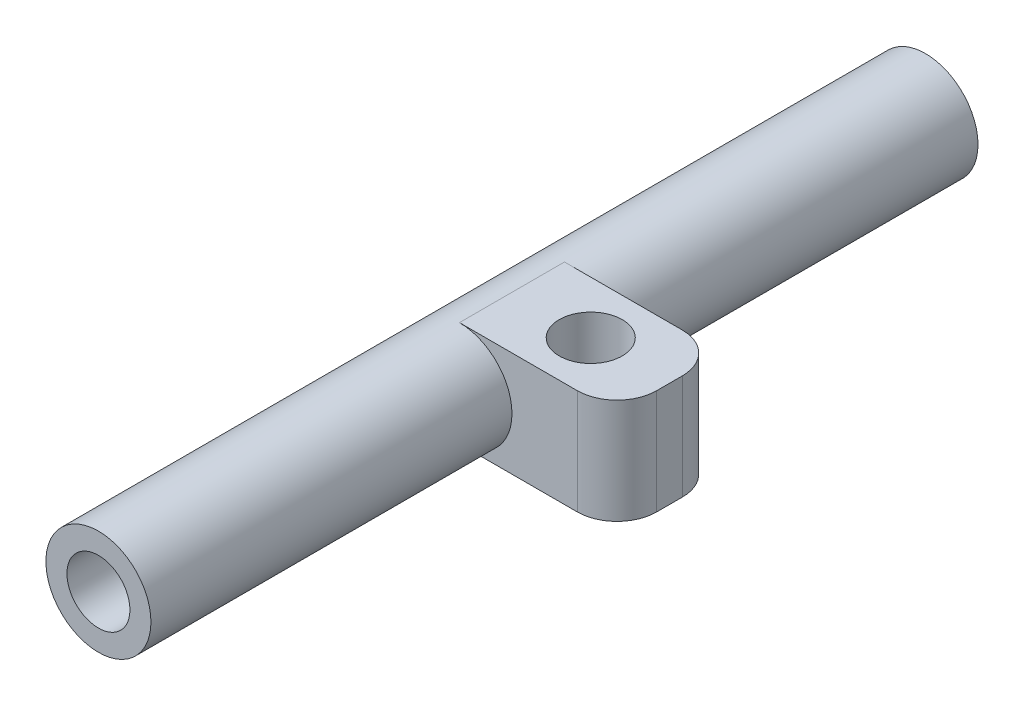
SolidWorks part; units mm, degrees
ref_plane "Front Plane" through (0, 0, 0) normal (0, 0, 1) x (1, 0, 0)
ref_plane "Top Plane" through (0, 0, 0) normal (0, 1, 0) x (1, 0, 0)
ref_plane "Right Plane" through (0, 0, 0) normal (1, 0, 0) x (0, 0, -1)
sketch "Sketch1" plane through (0, 0, 0) normal (0, 0, 1) x (1, 0, 0)
  line L0 (15.875, 0) -> (47.625, 0) construction
  line L1 (47.625, -15.875) -> (47.625, 15.875)
  line L2 (47.625, 15.875) -> (0, 15.875)
  line L3 (47.625, -15.875) -> (0, -15.875)
  circle A0 centre (0, 0) radius 9.525
  circle A1 centre (0, 0) radius 15.875
  point P9 (47.625, 0)
  dimension "D1" = 19.05
  dimension "D2" = 31.75
  dimension "D3" = 31.75
extrude "Boss-Extrude1" add sketch "Sketch1" along normal mid plane 250 contours A1 A0 region at (-15.426, 0, 0)
extrude "Boss-Extrude2" add sketch "Sketch1<3>" along normal mid plane 31.75 contours L0 A1 L3 L1 | A1 L0 L1 L2 region at (29.868, 8.3631, 0) region at (29.868, -8.3631, 0)
sketch "Sketch1<3>" plane through (0, 0, 0) normal (0, 0, 1) x (1, 0, 0) same geometry as "Sketch1"
sketch "Sketch2" plane through (0, 15.875, 0) normal (0, 1, 0) x (1, 0, 0)
  line L0 (0, 0) -> (47.625, 0) construction
  line L1 (0, -15.875) -> (0, 15.875) construction
  line L2 (47.625, -15.875) -> (47.625, 15.875) construction
  circle A0 centre (23.8125, 0) radius 9.525
  dimension "D1" = 19.05
extrude "Cut-Extrude1" cut sketch "Sketch2" against normal blind 25.4
fillet "Fillet1" radius 12 2 edges at (47.625, 0, -15.875) (47.625, 0, 15.875)
